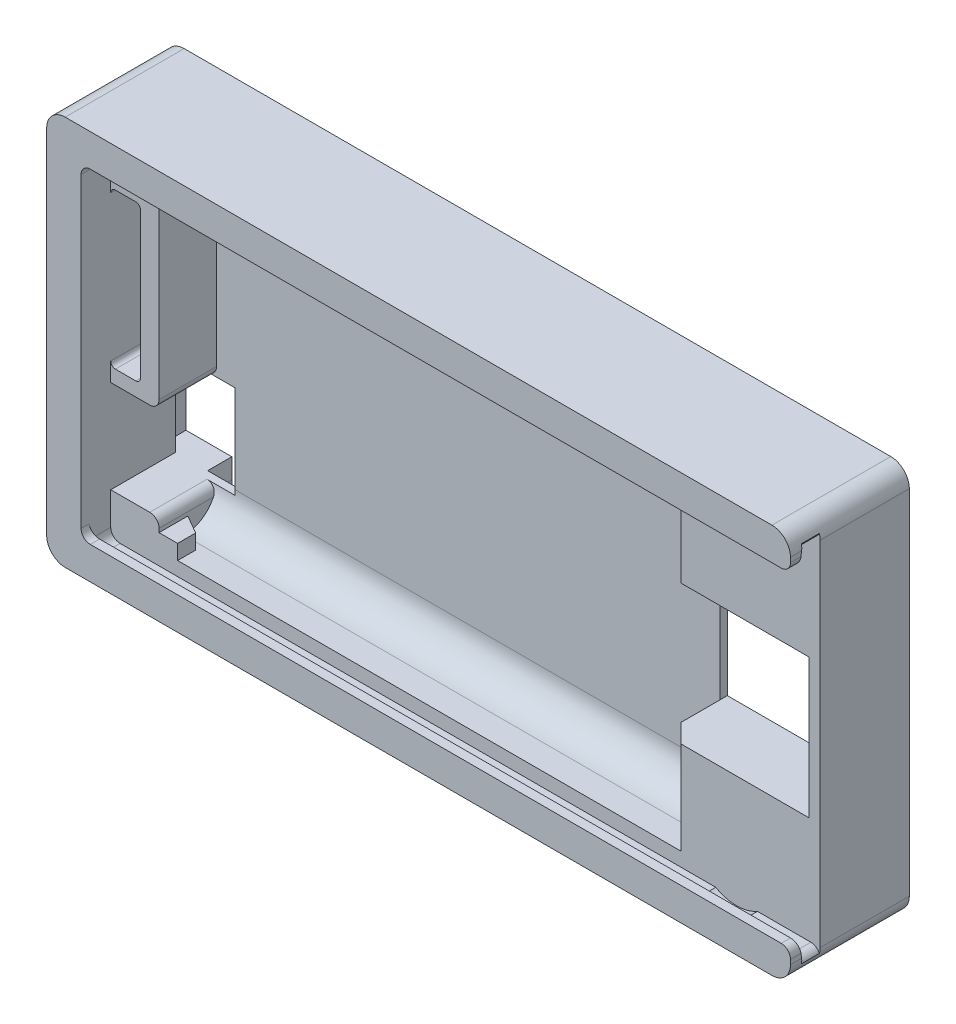
SolidWorks part; units mm, degrees
ref_plane "Front Plane" through (0, 0, 0) normal (0, 0, 1) x (1, 0, 0)
ref_plane "Top Plane" through (0, 0, 0) normal (0, 1, 0) x (1, 0, 0)
ref_plane "Right Plane" through (0, 0, 0) normal (1, 0, 0) x (0, 0, -1)
sketch "Sketch1" plane through (0, 0, 0) normal (0, 0, 1) x (1, 0, 0)
  line L1 (-26.5, 17) -> (26.5, 17)
  line L2 (-26.5, 17) -> (-26.5, -17)
  line L3 (-26.5, -17) -> (26.5, -17)
  line L4 (26.5, 17) -> (26.5, -17)
  line L5 (-26.5, 17) -> (26.5, -17) construction
  line L6 (-26.5, -17) -> (26.5, 17) construction
  point P0 (0, 0)
  dimension "D1" = 34
  dimension "D2" = 53
sketch "Sketch2" plane through (0, 0, 0) normal (0, 0, 1) x (1, 0, 0)
  line L1 (-32.3, 19) -> (44.1, 19)
  line L2 (-32.3, 19) -> (-32.3, -19)
  line L3 (-32.3, -19) -> (44.1, -19)
  line L4 (44.1, 19) -> (44.1, -19)
  line L6 (-26.5, 17) -> (-26.5, -17) construction
  line L7 (26.5, 17) -> (26.5, -17) construction
  line L8 (-26.5, -17) -> (-26.5, -19) construction
  line L9 (-26.5, 17) -> (-26.5, 19) construction
  line L10 (-26.5, 17) -> (26.5, 17) construction
  dimension "D1" = 5.8
  dimension "D2" = 17.6
  dimension "D3" = 2
extrude "Boss-Extrude1" add sketch "Sketch2" along normal blind 7
sketch "Sketch3" plane through (0, 0, 0) normal (1, 0, 0) x (0, 0, -1)
  line L0 (-7.3, 17) -> (-4.3, 17) construction
  line L1 (-1.3, 0) -> (-7.3, 0) construction
  line L2 (-7.3, -17) -> (-7.3, 17) construction
  line L3 (-1.3, -14) -> (-1.3, 14) construction
  line L4 (-7.3, -17) -> (-4.3, -17) construction
  line L5 (-7.8, 17.5) -> (-4.3, 17.5)
  line L6 (-0.8, -14) -> (-0.8, 14)
  line L7 (-7.8, -17.5) -> (-4.3, -17.5)
  line L8 (-7.8, -17.5) -> (-7.8, 17.5)
  arc A0 (-4.3, 17) -> (-1.3, 14) centre (-4.3, 14) cw construction
  arc A1 (-4.3, -17) -> (-1.3, -14) centre (-4.3, -14) ccw construction
  arc A2 (-4.3, 17.5) -> (-0.8, 14) centre (-4.3, 14) cw
  arc A3 (-4.3, -17.5) -> (-0.8, -14) centre (-4.3, -14) ccw
  dimension "D1" = 3
  dimension "D2" = 6
  dimension "D3" = 34
  dimension "D5" = 0.8
  dimension "D4" = 0.5
extrude "Cut-Battery" cut sketch "Sketch3" against normal mid plane 54.2
sketch "Sketch4" plane through (0, 0, 7) normal (0, 0, 1) x (1, 0, 0)
  line L1 (0, 0) -> (34, 0) construction
  line L2 (40.9, 7.5) -> (27.1, 7.5)
  line L3 (40.9, 7.5) -> (40.9, -7.5)
  line L4 (40.9, -7.5) -> (27.1, -7.5)
  line L7 (27.1, 7.5) -> (27.1, -7.5)
  line L8 (40.9, 7.5) -> (27.1, -7.5) construction
  line L9 (40.9, -7.5) -> (27.1, 7.5) construction
  line L10 (27.1, -14) -> (27.1, 14) construction
  line L12 (27.1, 17.5) -> (27.1, -17.5) construction
  line L13 (44.1, -19) -> (44.1, 19) construction
  point P0 (34, 0)
  dimension "D1" = 15
  dimension "D2" = 3.2
extrude "Cut for finger" cut sketch "Sketch4" against normal through all
chamfer "Chamfer3" distance 2 distance2 7 1 edges at (40.9, 0, 7) first distance on face at (17, 0, 7)
sketch "Sketch5" plane through (0, 17.5, 0) normal (0, -1, 0) x (1, 0, 0)
  line L0 (-27.1, 7) -> (-25.1, 7)
  line L1 (27.1, 7) -> (-27.1, 7) construction
  line L2 (-25.1, 7) -> (-25.1, 3.9)
  line L3 (-25.1, 3.9) -> (-27.1, 3.9)
  line L4 (-27.1, 3.9) -> (-27.1, 7)
  line L5 (-26.9, 3.8) -> (-24.9, 3.8) construction
  line L6 (-24.9, 3.8) -> (-24.9, 6.8) construction
  line L7 (-24.9, 6.8) -> (-20.5432, 6.8) construction
  line L8 (-26.9, 3.8) -> (-26.9, 0.8) construction
  line L9 (-26.9, 0.8) -> (-20.5432, 0.8) construction
  line L10 (-20.5432, 0.8) -> (-20.5432, 6.8) construction
  line L11 (-27.1, 0.8) -> (27.1, 0.8) construction
  line L12 (-27.1, 0.8) -> (-27.1, 4.3) construction
  dimension "D1" = 6
  dimension "D2" = 3
  dimension "D3" = 0.2
  dimension "D4" = 2
  dimension "D5" = 0.2
  dimension "D6" = 0.1
extrude "Boss-Extrude2" add sketch "Sketch5" along normal blind 1.6
chamfer "Chamfer1" distance 2 angle 30 1 edges at (-25.1, 16.6885, 3.9) first distance on face at (-26.1, 16.6885, 3.9)
mirror "Mirror1" about plane through (0, 0, 0) normal (0, 1, 0) of "Chamfer1", "Boss-Extrude2"
sketch "Sketch6" plane through (0, 0, 7) normal (0, 0, 1) x (1, 0, 0)
  line L1 (-32.3, -4.5) -> (-25.1, -4.5)
  line L2 (-32.3, -4.5) -> (-32.3, -14.5)
  line L3 (-32.3, -14.5) -> (-25.1, -14.5)
  line L4 (-25.1, -4.5) -> (-25.1, -14.5)
  line L7 (-26.5, -17) -> (26.5, -17) construction
  line L8 (-32.3, 19) -> (-32.3, -19) construction
  point P8 (-32.3, -9.5)
  dimension "D1" = 10
  dimension "D2" = 7.5
  dimension "D3" = 7.2
extrude "Cut-Connector" cut sketch "Sketch6" against normal through all
sketch "Sketch9" plane through (0, 0, 0) normal (0, 0, 1) x (1, 0, 0)
  line L0 (44.1, -19) -> (-32.3, -19)
  line L1 (-32.3, -19) -> (-32.3, 19)
  line L2 (-32.3, 19) -> (44.1, 19)
  line L3 (44.1, 19) -> (44.1, 21)
  line L4 (44.1, 21) -> (-34.3, 21)
  line L5 (-34.3, 21) -> (-34.3, -21)
  line L6 (-34.3, -21) -> (44.1, -21)
  line L7 (44.1, -21) -> (44.1, -19)
  line L8 (44.1, -19) -> (44.1, 19) construction
  dimension "D1" = 2
  dimension "D2" = 2
extrude "Boss-Extrude3" add sketch "Sketch9" along normal offset from surface (10.2 mm away) 3.2 up to face at (-2.78, -1.9, 7) offset beyond the face yes
sketch "Sketch10" plane through (0, 0, 7) normal (0, 0, 1) x (1, 0, 0)
  line L0 (44.1, 19) -> (44.1, 21) construction
  line L1 (13.6743, 19.6) -> (35.1, 19.6) construction
  line L3 (-32.3, 19) -> (44.1, 19) construction
  line L4 (0, 0) -> (44.1, 0) construction
  line L5 (44.1, -19) -> (44.1, 19) construction
  circle A0 centre (35.1, 15.1) radius 4.5
  circle A1 centre (35.1, -15.1) radius 4.5
  dimension "D1" = 9
  dimension "D2" = 9
  dimension "D3" = 0.6
  dimension "D4" = 15.1
extrude "Cut-Latch" cut sketch "Sketch10" along normal blind 2
sketch "Sketch11" plane through (44.1, 0, 0) normal (1, 0, 0) x (0, 0, -1)
  line L0 (-10.2, 19) -> (-9, 19)
  line L1 (-10.2, 19) -> (-7, 19) construction
  line L2 (-9, 19) -> (-9.2, 17.5)
  line L3 (-9.2, 17.5) -> (-10.2, 17.5)
  line L4 (-10.2, -19) -> (-10.2, 19) construction
  line L5 (-10.2, 17.5) -> (-10.2, 19)
  line L8 (0, 0) -> (-12.817, 0) construction
  line L9 (-9.2, -17.5) -> (-10.2, -17.5)
  line L10 (-9, -19) -> (-9.2, -17.5)
  line L11 (-10.2, -19) -> (-9, -19)
  line L12 (-10.2, -17.5) -> (-10.2, -19)
  dimension "D1" = 1
  dimension "D2" = 38
  dimension "D3" = 82.405
  dimension "D4" = 1.5
  dimension "D5" = 1.2
extrude "Boss-Extrude4" add sketch "Sketch11" against normal up to surface (76.4 mm away) up to face at (-32.3, -4.75, 6.05)
fillet "Fillet3" radius 1 2 edges at (44.1, -19, 8) (44.1, 19, 8)
chamfer "Chamfer2" distance 2 angle 45 2 edges at (27.1, -12.5, 7) (27.1, 12.5, 7)
fillet "Fillet2" radius 1 2 edges at (-27.1, -14.5, 3.9179) (-27.1, -4.5, 3.9)
sketch "Sketch12" plane through (0, 0, 7) normal (0, 0, 1) x (1, 0, 0)
  line L0 (-28.1, -4.5) -> (-32.3, -4.5) construction
  line L1 (-32.3, 13.7) -> (-29.1, 13.7)
  line L2 (-32.3, 13.7) -> (-32.3, -3)
  line L3 (-32.3, -3) -> (-29.1, -3)
  line L4 (-29.1, 13.7) -> (-29.1, -3)
  line L5 (-27.1, -3.5) -> (-27.1, 14) construction
  line L6 (-32.3, 19) -> (-32.3, -4.5) construction
  dimension "D1" = 1.5
  dimension "D2" = 2
  dimension "D3" = 3.2
  dimension "D4" = 16.7
extrude "Cut-Extrude6" cut sketch "Sketch12" against normal through all
fillet "Fillet1" radius 0.5 4 edges at (-29.1, 13.7, 3.5) (-32.3, 13.7, 3.5) (-32.3, -3, 3.5) (-29.1, -3, 3.5)
sketch "Sketch13" plane through (0, 0, 0) normal (0, 0, -1) x (-1, 0, 0)
  line L0 (33.8, 17.35) -> (33.8, -17.35) construction
  line L1 (34.3, 21) -> (36, 21)
  line L2 (34.3, 21) -> (34.3, -21)
  line L3 (34.3, -21) -> (36, -21)
  line L4 (36, 21) -> (36, -21)
  dimension "D1" = 2.2
extrude "Boss-Extrude5" add sketch "Sketch13" against normal up to surface (10.2 mm away) up to face at (5.4, 0, 10.2)
sketch "Sketch16" plane through (0, 0, 0) normal (0, 0, -1) x (-1, 0, 0)
  circle A0 centre (-39.55, 16.4) radius 1.1
  circle A1 centre (31.45, 16.4) radius 1.1
  circle A2 centre (31.45, -16.4) radius 1.1
  circle A3 centre (-39.55, -16.4) radius 1.1
  circle A4 centre (-39.55, 16.4) radius 1.25 construction
  circle A5 centre (31.45, 16.4) radius 1.25 construction
  circle A6 centre (31.45, -16.4) radius 1.25 construction
  circle A7 centre (-39.55, -16.4) radius 1.25 construction
  dimension "D1" = 2.2
extrude "Cut-Extrude7" cut sketch "Sketch16" against normal offset from surface (3 mm away) 4 up to face at (-3.3881, -0.3944, 7)
sketch "Sketch18" plane through (0, 0, 0) normal (0, 0, -1) x (-1, 0, 0)
  line L0 (-35.9671, 17.75) -> (27.8671, 17.75)
  line L1 (-41.9, 18.75) -> (33.8, 18.75)
  line L2 (-41.9, 18.75) -> (-41.9, -18.75)
  line L3 (-41.9, -18.75) -> (33.8, -18.75)
  line L4 (33.8, 18.75) -> (33.8, -18.75)
  line L5 (-40.9, 12.8171) -> (-40.9, -12.8171)
  line L6 (-41.9, 14.178) -> (-40.9, 14.178) construction
  line L7 (-37.328, 17.75) -> (-37.328, 18.75) construction
  line L8 (-41.9, 0) -> (33.8, 0) construction
  line L9 (-4.05, 18.75) -> (-4.05, -18.75) construction
  line L10 (-35.9671, -17.75) -> (27.8671, -17.75)
  line L11 (32.8, 12.8171) -> (32.8, -12.8171)
  line L12 (28.8623, -16.6528) -> (28.8623, -14.5)
  line L13 (32.3, -14.5) -> (25.1, -14.5) construction
  line L14 (28.8623, -14.5) -> (32.8, -14.5)
  line L15 (32.8, -14.5) -> (32.8, -12.8171)
  line L16 (-40.5, 18.75) -> (32.4, 18.75) construction
  line L17 (-41.9, -17.35) -> (-41.9, 17.35) construction
  line L18 (33.8, 17.35) -> (33.8, -17.35) construction
  line L19 (32.4, -18.75) -> (-40.5, -18.75) construction
  arc A0 (-36.9623, 16.6528) -> (-39.8028, 13.8123) centre (-39.55, 16.4) cw
  arc A1 (-36.9623, 16.6528) -> (-35.9671, 17.75) centre (-35.9671, 16.75) cw
  arc A2 (-39.8028, 13.8123) -> (-40.9, 12.8171) centre (-39.9, 12.8171) ccw
  circle A3 centre (-39.55, 16.4) radius 1.1
  circle A4 centre (-39.55, 16.4) radius 1.1 construction
  circle A5 centre (-39.55, -16.4) radius 1.1
  arc A6 (-39.8028, -13.8123) -> (-40.9, -12.8171) centre (-39.9, -12.8171) cw
  arc A7 (-36.9623, -16.6528) -> (-35.9671, -17.75) centre (-35.9671, -16.75) ccw
  arc A8 (-36.9623, -16.6528) -> (-39.8028, -13.8123) centre (-39.55, -16.4) ccw
  arc A10 (28.8623, -16.6528) -> (27.8671, -17.75) centre (27.8671, -16.75) cw
  circle A12 centre (31.45, -16.4) radius 1.1
  circle A13 centre (31.45, 16.4) radius 1.1
  arc A14 (31.7028, 13.8123) -> (32.8, 12.8171) centre (31.8, 12.8171) cw
  arc A15 (28.8623, 16.6528) -> (27.8671, 17.75) centre (27.8671, 16.75) ccw
  arc A16 (28.8623, 16.6528) -> (31.7028, 13.8123) centre (31.45, 16.4) ccw
  point P36 (-40.9, 0)
  point P38 (-4.05, 17.75)
  point P39 (-4.05, -17.75)
  point P53 (32.8, 0)
  point P60 (33.4835, -18.6195)
  dimension "D2" = 2.6
  dimension "D3" = 1
  dimension "D1" = 1
extrude "PCB stand" add sketch "Sketch18" along normal blind 2.6
sketch "Sketch19" plane through (0, 0, -2.6) normal (0, 0, -1) x (-1, 0, 0)
  line L0 (33.8, -18.75) -> (33.8, 18.75) construction
  line L1 (32.8, -14.5) -> (33.8, -14.5)
  line L2 (32.8, -14.5) -> (32.8, -4.5)
  line L3 (32.8, -4.5) -> (33.8, -4.5)
  line L4 (33.8, -14.5) -> (33.8, -4.5)
  line L5 (25.1, -4.5) -> (32.3, -4.5) construction
extrude "Cut-Extrude8" cut sketch "Sketch19" against normal up to surface (2.6 mm away) up to face at (-30.7, 5.35, 0)
hole_wizard "Ø2.0mm Dowel Hole1" positions "Sketch20" profile "Sketch21" hole size "Ø2.0" standard "DIN"
sketch "Sketch20" plane through (0, 0, -2.6) normal (0, 0, -1) x (-1, 0, 0)
  point P0 (-39.55, -16.4)
  point P3 (-39.55, 16.4)
  point P6 (31.45, 16.4)
  point P9 (31.45, -16.4)
sketch "Sketch21" plane through (39.55, -16.4, -2.6) normal (1, 0, 0) x (0, 1, 0)
  line L0 (0, 0) -> (0, 9.4053)
  line L1 (0, 9.4053) -> (1.1, 7.5)
  line L2 (1.1, 7.5) -> (1.1, 0)
  line L5 (1.1, 0) -> (0, 0)
  line L10 (0, 9.4053) -> (-1.1, 7.5) construction
  line L11 (0, -6.35) -> (0, 107.95) construction
  dimension "Hole Dia." = 2.2
  dimension "Hole Depth" = 7.5
  dimension "Drill Angle" = 60
sketch "Sketch22" plane through (0, 0, 0) normal (0, 0, -1) x (-1, 0, 0)
  line L1 (36, -21) -> (-44.1, -21)
  line L2 (36, -21) -> (36, 21)
  line L3 (36, 21) -> (-44.1, 21)
  line L4 (-44.1, -21) -> (-44.1, 21)
  line L5 (-41.9, 18.75) -> (33.8, 18.75)
  line L6 (-41.9, 18.75) -> (-41.9, -18.75)
  line L7 (-41.9, -18.75) -> (33.8, -18.75)
  line L8 (33.8, 18.75) -> (33.8, -18.75)
extrude "Boss-Extrude8" add sketch "Sketch22" along normal up to surface (2.6 mm away) up to face at (0.7177, -0.5363, -2.6)
fillet "Fillet4" radius 2 4 edges at (44.1, 21, 3.8) (44.1, -21, 3.8) (-36, -21, 3.8) (-36, 21, 3.8)
fillet "Fillet5" radius 1 2 edges at (44.1, -17.5, 9.7) (44.1, 17.5, 9.7)
fillet "Fillet6" radius 1 2 edges at (-32.3, 17.5, 9.7) (-32.3, -17.5, 9.7)
fillet "Fillet7" radius 1 2 edges at (-32.3, -19, 8) (-32.3, 19, 8)
equation "\"D1@Cut-Battery\" = 53 / 2 + 0.6"
